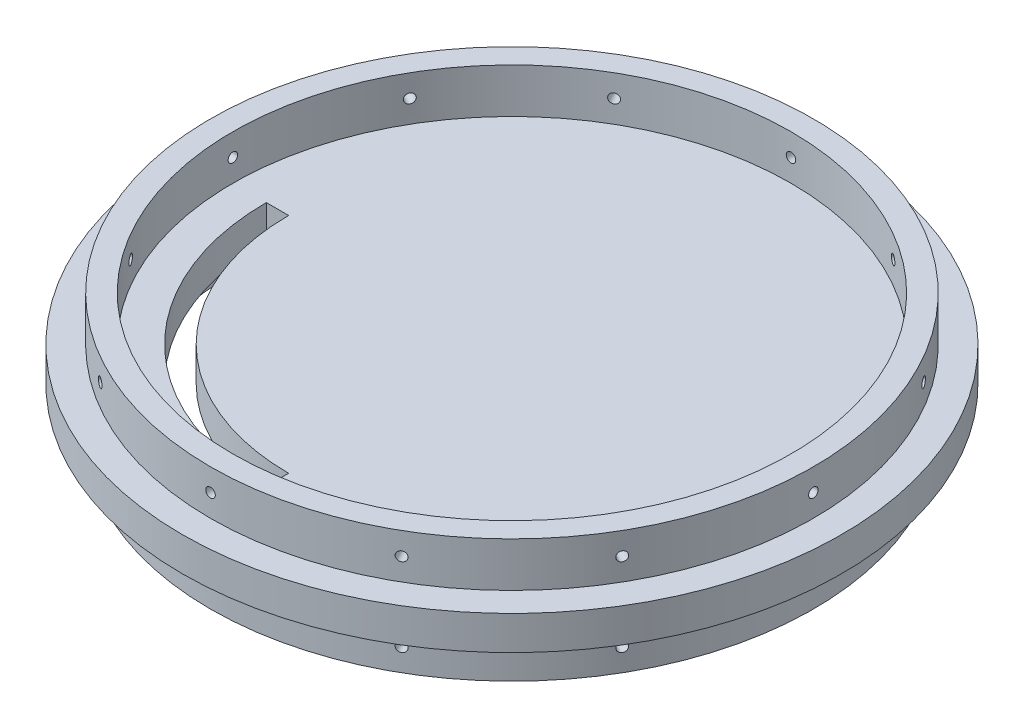
SolidWorks part; units mm, degrees
material "6061-T6 (SS)"
ref_plane "Front Plane" through (0, 0, 0) normal (0, 0, 1) x (1, 0, 0)
ref_plane "Top Plane" through (0, 0, 0) normal (0, 1, 0) x (1, 0, 0)
ref_plane "Right Plane" through (0, 0, 0) normal (1, 0, 0) x (0, 0, -1)
sketch "Sketch1" plane through (0, 0, 0) normal (0, 1, 0) x (1, 0, 0)
  circle A0 centre (0, 0) radius 93.726
  dimension "D1" = 187.452
extrude "Boss-Extrude1" add sketch "Sketch1" along normal mid plane 9.652
sketch "Sketch2" plane through (0, 0, 0) normal (0, 0, 1) x (1, 0, 0)
  line L0 (0, -18.3275) -> (0, 20.8308) construction
  line L1 (0, -4.826) -> (-19.297, -4.826)
  line L2 (-93.726, -4.826) -> (93.726, -4.826) construction
  line L3 (0, -4.826) -> (0, -1.4952)
  line L4 (-0.3818, -1.4952) -> (0, -1.4952)
  arc A0 (-19.297, -4.826) -> (-0.3818, -1.4952) centre (-0.4072, -56.7254) cw
  dimension "D6" = 55.2302
  dimension "D1" = 19.297
  dimension "D2" = 3.3308
  dimension "D3" = 0.3818
revolve "Cut-Revolve1" cut sketch "Sketch2" angle 360 about L0
sketch "Sketch4" plane through (0, 4.826, 0) normal (0, 1, 0) x (1, 0, 0)
  circle A0 centre (0, 0) radius 85.725
  circle A1 centre (0, 0) radius 79.375
  dimension "D1" = 171.45
  dimension "D2" = 158.75
extrude "Boss-Extrude2" add sketch "Sketch4" along normal blind 12.7
ref_plane "Plane1" through (0, 0, -85.725) normal (0, 0, -1) x (-1, 0, 0)
sketch "Sketch5" plane through (0, 0, -85.725) normal (0, 0, -1) x (-1, 0, 0)
  line L0 (0, 12.2936) -> (0, -12.2936) construction
  line L1 (79.375, 17.526) -> (-79.375, 17.526) construction
  circle A0 centre (0, 11.176) radius 1.3525
  dimension "D1" = 2.7051
  dimension "D2" = 6.35
extrude "Cut-Extrude2" cut sketch "Sketch5" against normal blind 12.7
pattern_circular "CirPattern1" count 12 over 360 about axis through (0, 17.526, 0) along (0, -1, 0) of "Cut-Extrude2" reverse direction yes
mirror "Mirror2" about plane through (0, 0, 0) normal (0, 1, 0) of "CirPattern1", "Cut-Extrude2", "Boss-Extrude2"
sketch "Sketch6" plane through (0, 4.826, 0) normal (0, 1, 0) x (1, 0, 0)
  line L0 (-63.5, 0) -> (-69.85, 0)
  line L1 (0, -69.85) -> (0, -63.5)
  line L2 (0, -12.2936) -> (0, 12.2936) construction
  arc A0 (-69.85, 0) -> (0, -69.85) centre (0, 0) ccw
  arc A1 (-63.5, 0) -> (0, -63.5) centre (0, 0) ccw
  dimension "D1" = 69.85
  dimension "D2" = 63.5
  dimension "D3" = 90
extrude "Cut-Extrude3" cut sketch "Sketch6" against normal up to surface (9.652 mm away) up to face at (0, -4.826, -19.297)
